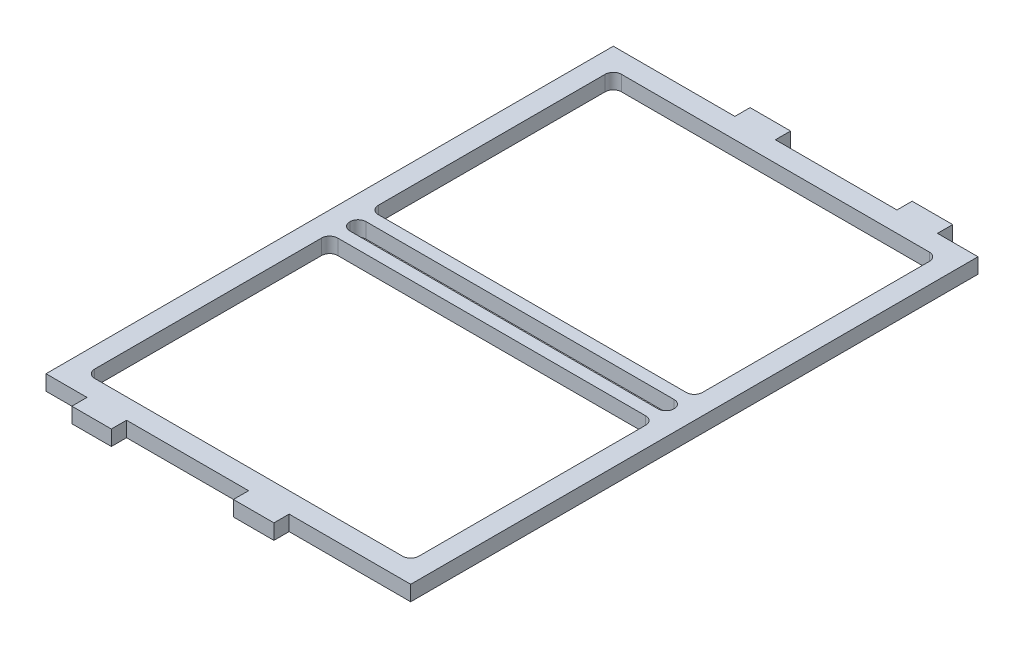
SolidWorks part; units mm, degrees
material "6061-T6 (SS)"
ref_plane "Front Plane" through (0, 0, 0) normal (0, 0, 1) x (1, 0, 0)
ref_plane "Top Plane" through (0, 0, 0) normal (0, 1, 0) x (1, 0, 0)
ref_plane "Right Plane" through (0, 0, 0) normal (1, 0, 0) x (0, 0, -1)
sketch "Sketch1" plane through (0, 0, 0) normal (0, 1, 0) x (1, 0, 0)
  line L0 (50.8, 82.55) -> (-50.8, 82.55)
  line L1 (57.15, 88.9) -> (-57.15, 88.9)
  line L2 (57.15, 88.9) -> (57.15, -88.9)
  line L3 (57.15, -88.9) -> (-57.15, -88.9)
  line L4 (-57.15, 88.9) -> (-57.15, -88.9)
  line L5 (57.15, 88.9) -> (-57.15, -88.9) construction
  line L6 (57.15, -88.9) -> (-57.15, 88.9) construction
  line L7 (-50.8, 82.55) -> (-50.8, -82.55)
  line L8 (50.8, -82.55) -> (-50.8, -82.55)
  line L9 (50.8, 82.55) -> (50.8, -82.55)
  point P0 (0, 0)
  dimension "D1" = 114.3
  dimension "D2" = 177.8
  dimension "D3" = 6.35
extrude "Boss-Extrude1" add sketch "Sketch1" along normal blind 4.7625
sketch "Sketch2" plane through (0, 0, 88.9) normal (0, 0, 1) x (1, 0, 0)
  line L0 (-57.15, 2.3813) -> (57.15, 2.3813) construction
  line L1 (-57.15, 4.7625) -> (-57.15, 0) construction
  line L2 (57.15, 4.7625) -> (57.15, 0) construction
  line L3 (-57.15, 0) -> (57.15, 0) construction
  line L4 (-31.9066, 4.7625) -> (-44.2934, 4.7625)
  line L5 (-31.9066, 4.7625) -> (-31.9066, 0)
  line L6 (-31.9066, 0) -> (-44.2934, 0)
  line L7 (-44.2934, 4.7625) -> (-44.2934, 0)
  line L8 (-31.9066, 4.7625) -> (-44.2934, 0) construction
  line L9 (-31.9066, 0) -> (-44.2934, 4.7625) construction
  line L11 (19.05, 4.7625) -> (6.35, 4.7625)
  line L12 (19.05, 4.7625) -> (19.05, 0)
  line L13 (19.05, 0) -> (6.35, 0)
  line L14 (6.35, 4.7625) -> (6.35, 0)
  line L15 (19.05, 4.7625) -> (6.35, 0) construction
  line L16 (19.05, 0) -> (6.35, 4.7625) construction
  point P6 (-38.1, 2.3813)
  point P13 (12.7, 2.3813)
  dimension "D1" = 19.05
  dimension "D2" = 50.8
  dimension "D3" = 12.7
extrude "Boss-Extrude2" add sketch "Sketch2" along normal blind 4.7625
sketch "Sketch3" plane through (0, 0, -88.9) normal (0, 0, -1) x (-1, 0, 0)
  line L0 (-57.15, 2.3813) -> (57.15, 2.3813) construction
  line L1 (-57.15, 4.7625) -> (-57.15, 0) construction
  line L2 (57.15, 4.7625) -> (57.15, 0) construction
  line L3 (-57.15, 0) -> (57.15, 0) construction
  line L4 (-31.75, 4.7625) -> (-44.45, 4.7625)
  line L5 (-31.75, 4.7625) -> (-31.75, 0)
  line L6 (-31.75, 0) -> (-44.45, 0)
  line L7 (-44.45, 4.7625) -> (-44.45, 0)
  line L8 (-31.75, 4.7625) -> (-44.45, 0) construction
  line L9 (-31.75, 0) -> (-44.45, 4.7625) construction
  line L11 (19.05, 4.7625) -> (6.35, 4.7625)
  line L12 (19.05, 4.7625) -> (19.05, 0)
  line L13 (19.05, 0) -> (6.35, 0)
  line L14 (6.35, 4.7625) -> (6.35, 0)
  line L15 (19.05, 4.7625) -> (6.35, 0) construction
  line L16 (19.05, 0) -> (6.35, 4.7625) construction
  point P6 (-38.1, 2.3812)
  point P13 (12.7, 2.3812)
  dimension "D1" = 12.7
  dimension "D2" = 12.7
  dimension "D3" = 19.05
  dimension "D4" = 50.8
extrude "Boss-Extrude3" add sketch "Sketch3" along normal blind 4.7625
fillet "Fillet1" radius 2.54 4 edges at (50.8, 2.3813, 82.55) (50.8, 2.3813, -82.55) (-50.8, 2.3813, -82.55) (-50.8, 2.3813, 82.55)
sketch "Sketch4" plane through (0, 0, 0) normal (0, -1, 0) x (1, 0, 0)
  line L0 (-48.26, 82.55) -> (48.26, 82.55) construction
  line L1 (-6.35, -82.55) -> (6.35, -82.55)
  line L2 (-6.35, -82.55) -> (-6.35, 82.55)
  line L3 (-6.35, 82.55) -> (6.35, 82.55)
  line L4 (6.35, -82.55) -> (6.35, 82.55)
  line L5 (-6.35, -82.55) -> (6.35, 82.55) construction
  line L6 (-6.35, 82.55) -> (6.35, -82.55) construction
  line L7 (2.54, 69.85) -> (-2.54, 69.85) construction
  line L8 (2.54, -69.85) -> (-2.54, -69.85) construction
  line L9 (-2.54, -69.85) -> (-2.54, 69.85)
  line L11 (2.54, -69.85) -> (2.54, 69.85)
  line L12 (-2.54, -69.85) -> (2.54, 69.85) construction
  line L13 (-2.54, 69.85) -> (2.54, -69.85) construction
  arc A0 (2.54, -69.85) -> (-2.54, -69.85) centre (0, -69.85) cw
  arc A1 (2.54, 69.85) -> (-2.54, 69.85) centre (0, 69.85) ccw
  point P0 (0, 0)
  point P8 (0, 0)
  dimension "D1" = 12.7
  dimension "D2" = 5.08
  dimension "D3" = 139.7
extrude "Boss-Extrude4" [suppressed] add sketch "Sketch4" against normal blind 4.7625
fillet "Fillet2" [suppressed] radius 2.54
sketch "Sketch5" plane through (0, 0, 0) normal (0, -1, 0) x (1, 0, 0)
  line L0 (57.15, 88.9) -> (57.15, -88.9) construction
  line L1 (-57.15, -6.35) -> (57.15, -6.35)
  line L2 (-57.15, -6.35) -> (-57.15, 6.35)
  line L3 (-57.15, 6.35) -> (57.15, 6.35)
  line L4 (57.15, -6.35) -> (57.15, 6.35)
  line L5 (-57.15, -6.35) -> (57.15, 6.35) construction
  line L6 (-57.15, 6.35) -> (57.15, -6.35) construction
  line L8 (-50.8, -2.54) -> (50.8, -2.54)
  line L9 (-50.8, -2.54) -> (-50.8, 2.54)
  line L10 (-50.8, 2.54) -> (50.8, 2.54)
  line L11 (50.8, -2.54) -> (50.8, 2.54)
  line L12 (-50.8, -2.54) -> (50.8, 2.54) construction
  line L13 (-50.8, 2.54) -> (50.8, -2.54) construction
  point P0 (0, 0)
  point P8 (0, 0)
  dimension "D1" = 12.7
  dimension "D2" = 101.6
  dimension "D3" = 5.08
extrude "Boss-Extrude5" add sketch "Sketch5" against normal blind 4.7625
fillet "Fillet3" radius 2.54 8 edges at (50.8, 2.3813, 6.35) (-50.8, 2.3813, 6.35) (-50.8, 2.3813, -6.35) (50.8, 2.3813, -6.35) (50.8, 2.3813, -2.54) (50.8, 2.3813, 2.54) (-50.8, 2.3813, -2.54) (-50.8, 2.3813, 2.54)
